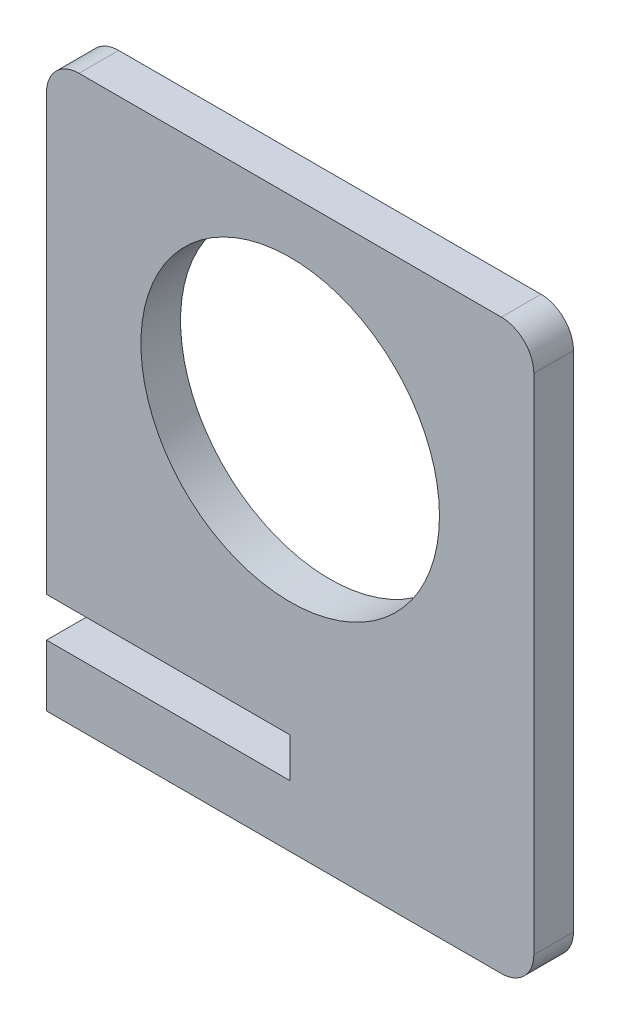
SolidWorks part; units mm, degrees
material "Corrugated Paper"
ref_plane "Front Plane" through (0, 0, 0) normal (0, 0, 1) x (1, 0, 0)
ref_plane "Top Plane" through (0, 0, 0) normal (0, 1, 0) x (1, 0, 0)
ref_plane "Right Plane" through (0, 0, 0) normal (1, 0, 0) x (0, 0, -1)
sketch "Sketch1" plane through (0, 0, 0) normal (0, 0, 1) x (1, 0, 0)
  line L0 (-19.05, 1.5494) -> (-19.05, 6.35)
  line L1 (-19.05, -1.5494) -> (0, -1.5494)
  line L3 (-19.05, 1.5494) -> (0, 1.5494)
  line L4 (0, -1.5494) -> (0, 1.5494)
  line L5 (-19.05, 6.35) -> (19.05, 6.35)
  line L6 (0, 0) -> (19.05, 0) construction
  line L7 (19.05, 6.35) -> (19.05, -6.35)
  line L8 (-19.05, -6.35) -> (19.05, -6.35)
  line L9 (-19.05, -1.5494) -> (-19.05, -6.35)
  line L10 (-19.05, 38.1) -> (19.05, 6.35) construction
  line L11 (-19.05, 6.35) -> (19.05, 6.35)
  line L12 (-19.05, 6.35) -> (-19.05, 38.1)
  line L13 (-19.05, 38.1) -> (19.05, 38.1)
  line L14 (19.05, 6.35) -> (19.05, 38.1)
  line L15 (19.05, 38.1) -> (-19.05, 6.35) construction
  circle A0 centre (0, 22.225) radius 11.6713
  dimension "D6" = 23.3426
  dimension "D1" = 19.05
  dimension "D2" = 3.0988
  dimension "D3" = 19.05
  dimension "D4" = 12.7
  dimension "D5" = 44.45
extrude "Boss-Extrude1" add sketch "Sketch1" along normal mid plane 3.0988 contours L5 L14 L13 L12 | L6 L4 L1 L9 L8 L7 | L4 L6 L7 L5 L0 L3 region at (1.3235, 0, 0) region at (-18.554, 22.225, 0)
fillet "Fillet1" radius 2.54 3 edges at (19.05, -6.35, 0) (-19.05, 38.1, 0) (19.05, 38.1, 0)
equation "\"D2@Sketch1\" = \"thick\""
equation "\"D1@Boss-Extrude1\"= \"thick\""
equation "\"rodThick\"= 0.085in"
equation "\"thick\"= 0.122in"
equation "\"D6@Sketch1\"=\"MotorDiameter@Motor-1.Part\""
